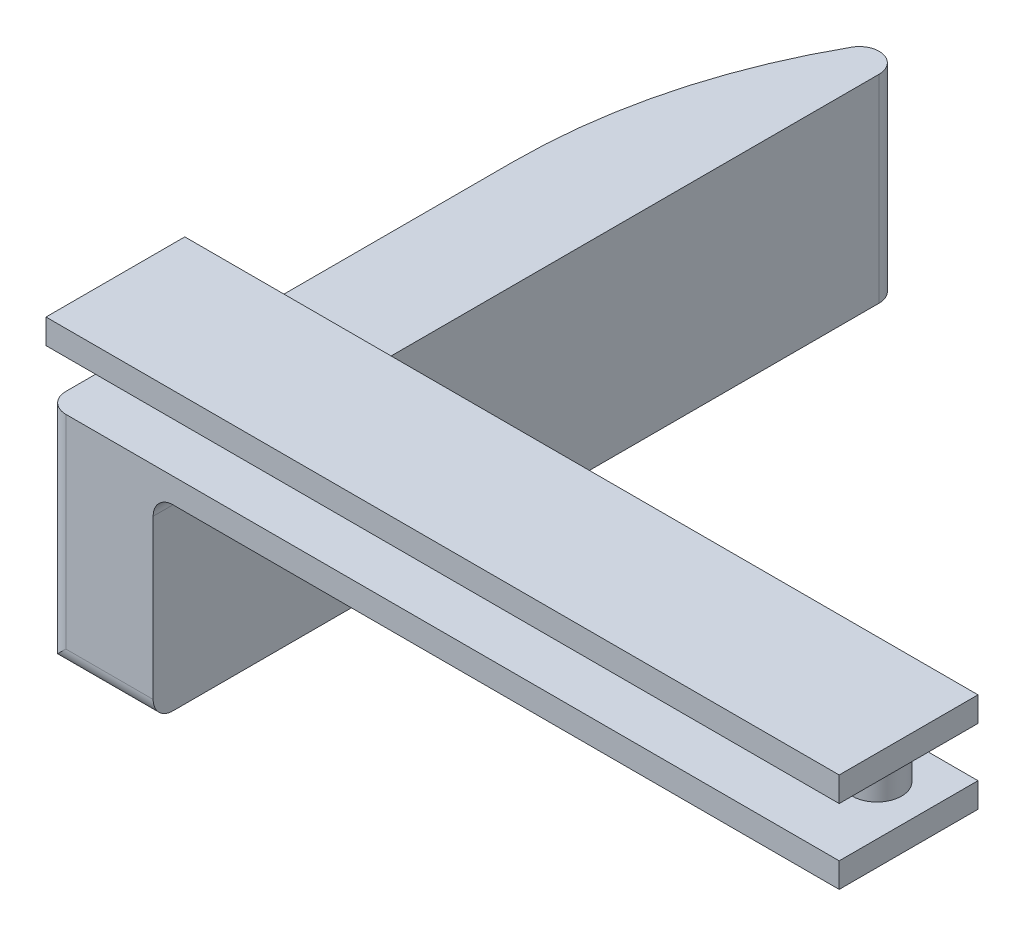
SolidWorks part; units mm, degrees
ref_plane "Front Plane" through (0, 0, 0) normal (0, 0, 1) x (1, 0, 0)
ref_plane "Top Plane" through (0, 0, 0) normal (0, 1, 0) x (1, 0, 0)
ref_plane "Right Plane" through (0, 0, 0) normal (1, 0, 0) x (0, 0, -1)
sketch "Sketch2" plane through (0, 0, 0) normal (0, 1, 0) x (1, 0, 0)
  line L1 (0, 0) -> (101.6, 0)
  line L2 (0, 0) -> (0, 17.78)
  line L3 (0, 17.78) -> (101.6, 17.78)
  line L4 (101.6, 0) -> (101.6, 17.78)
  dimension "D1" = 17.78
  dimension "D2" = 101.6
extrude "Boss-Extrude1" add sketch "Sketch2" along normal blind 3.175
sketch "Sketch3" plane through (0, 0, 0) normal (0, -1, 0) x (1, 0, 0)
  line L0 (95.25, -11.176) -> (6.35, -11.176) construction
  line L1 (95.25, -14.351) -> (6.35, -14.351)
  line L2 (95.25, -8.001) -> (6.35, -8.001)
  line L3 (0, 0) -> (101.6, 0) construction
  line L4 (0, -17.78) -> (0, 0) construction
  arc A0 (95.25, -14.351) -> (95.25, -8.001) centre (95.25, -11.176) ccw
  arc A1 (6.35, -8.001) -> (6.35, -14.351) centre (6.35, -11.176) ccw
  point P2 (50.8, -11.176)
  dimension "D1" = 88.9
  dimension "D2" = 11.176
  dimension "D3" = 6.35
  dimension "D4" = 6.35
extrude "Boss-Extrude2" add sketch "Sketch3" along normal blind 6.35 contours L2 A1 L1 A0
ref_plane "Plane1" through (0, -3.175, 0) normal (0, -1, 0) x (-1, 0, 0)
mirror "Mirror1" about plane through (0, -3.175, 0) normal (0, -1, 0) of "Boss-Extrude1"
sketch "Sketch5" plane through (0, -9.525, 0) normal (0, -1, 0) x (1, 0, 0)
  line L31 (0, 0) -> (13.7244, 0)
  line L32 (0, 0) -> (0, -59.8993)
  line L36 (13.7244, 0) -> (13.7244, -101.6)
  arc A2 (0, -59.8993) -> (13.7244, -101.6) centre (70.2144, -59.8993) ccw
  dimension "D1" = 101.6
extrude "Boss-Extrude3" add sketch "Sketch5" along normal blind 25.4
fillet "Fillet2" radius 2.54 1 edges at (13.7244, -22.225, -101.6)
fillet "Fillet3" radius 2.54 3 edges at (13.7244, -9.525, -8.89) (0, -20.6375, 0) (6.8622, -34.925, 0)
